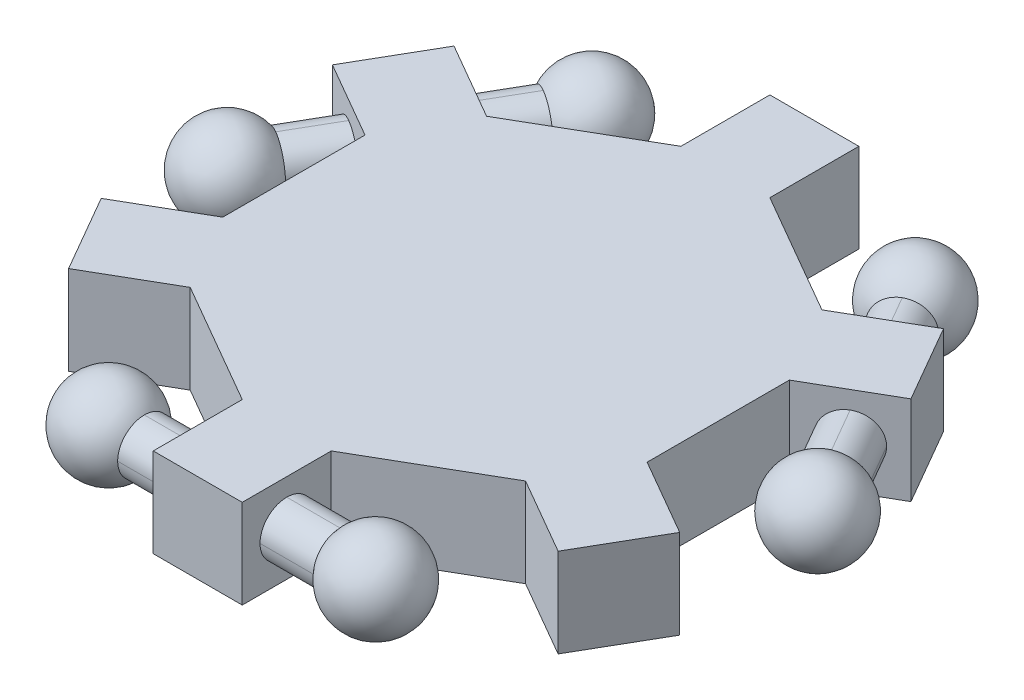
SolidWorks part; units mm, degrees
ref_plane "Front Plane" through (0, 0, 0) normal (0, 0, 1) x (1, 0, 0)
ref_plane "Top Plane" through (0, 0, 0) normal (0, 1, 0) x (1, 0, 0)
ref_plane "Right Plane" through (0, 0, 0) normal (1, 0, 0) x (0, 0, -1)
sketch "Sketch1" plane through (0, 0, 0) normal (0, 1, 0) x (1, 0, 0)
  line L0 (0, 210) -> (297, 0) construction
  line L1 (0, 0) -> (297, 0) construction
  line L2 (0, 0) -> (0, 210) construction
  line L3 (0, 210) -> (297, 210) construction
  line L4 (297, 0) -> (297, 210) construction
  line L5 (0, 0) -> (297, 210) construction
  dimension "D1" = 210
  dimension "D2" = 297
sketch "Sketch2" plane through (0, 0, 0) normal (0, 1, 0) x (1, 0, 0)
  line L0 (128.5, 139.641) -> (168.5, 139.641)
  line L1 (168.5, 139.641) -> (188.5, 105)
  line L2 (188.5, 105) -> (168.5, 70.359)
  line L3 (168.5, 70.359) -> (128.5, 70.359)
  line L4 (128.5, 70.359) -> (108.5, 105)
  line L5 (108.5, 105) -> (128.5, 139.641)
  line L6 (128.5, 139.641) -> (168.5, 70.359) construction
  line L7 (128.5, 70.359) -> (168.5, 139.641) construction
  line L8 (108.5, 105) -> (188.5, 105) construction
  line L9 (0, 0) -> (297, 0) construction
  line L10 (0, 210) -> (297, 0) construction
  line L11 (153.5, 139.641) -> (153.5, 129.641)
  line L12 (153.5, 129.641) -> (167.3397, 121.6506)
  line L13 (167.3397, 121.6506) -> (176, 126.6506)
  line L14 (143.5, 139.641) -> (143.5, 129.641)
  line L15 (143.5, 129.641) -> (129.6603, 121.6506)
  line L16 (129.6603, 121.6506) -> (121, 126.6506)
  line L17 (116, 117.9904) -> (128.9904, 110.4904)
  line L18 (128.9904, 110.4904) -> (124.6603, 97.0096)
  line L19 (124.6603, 97.0096) -> (116, 92.0096)
  line L20 (181, 117.9904) -> (172.3397, 112.9904)
  line L21 (172.3397, 112.9904) -> (172.3397, 97.0096)
  line L22 (172.3397, 97.0096) -> (181, 92.0096)
  line L23 (176, 83.3494) -> (167.3397, 88.3494)
  line L24 (167.3397, 88.3494) -> (153.5, 80.359)
  line L25 (153.5, 80.359) -> (153.5, 70.359)
  line L26 (121, 83.3494) -> (129.6603, 88.3494)
  line L27 (129.6603, 88.3494) -> (143.5, 80.359)
  line L28 (143.5, 80.359) -> (143.5, 70.359)
  point P2 (148.5, 105)
  point P11 (148.5, 105)
  dimension "D1" = 120
  dimension "D2" = 120
  dimension "D3" = 120
  dimension "D4" = 120
  dimension "D5" = 40
  dimension "D6" = 40
  dimension "D7" = 40
  dimension "D8" = 105
  dimension "D9" = 0
  dimension "D10" = 90
  dimension "D11" = 15
  dimension "D12" = 15
  dimension "D13" = 15
  dimension "D14" = 15
  dimension "D15" = 10
  dimension "D16" = 10
  dimension "D17" = 10
  dimension "D18" = 90
  dimension "D19" = 90
  dimension "D20" = 90
  dimension "D21" = 90
  dimension "D22" = 90
  dimension "D23" = 15
  dimension "D24" = 15
  dimension "D25" = 15
  dimension "D26" = 15
  dimension "D27" = 15
  dimension "D28" = 90
  dimension "D29" = 90
  dimension "D30" = 10
  dimension "D31" = 90
  dimension "D32" = 90
  dimension "D33" = 90
  dimension "D34" = 90
  dimension "D35" = 90
  dimension "D36" = 10
  dimension "D37" = 10
  dimension "D38" = 10
  dimension "D39" = 10
  dimension "D40" = 15
  dimension "D41" = 10
  dimension "D42" = 10
extrude "Boss-Extrude1" add sketch "Sketch2" along normal blind 10 contours L27 L28 L3 L25 L24 L23 L2 L22 L21 L20 L1 L13 L12 L11 L0 L14 L15 L16 L5 L17 L18 L19 L4 L26 region at (148.8166, 0, -104.9741)
sketch "Sketch3" plane through (153.5, 0, 0) normal (1, 0, 0) x (0, 0, -1)
  line L1 (0, 0) -> (210, 0) construction
  line L2 (80.359, 10) -> (80.359, 0) construction
  line L3 (72.359, 8) -> (78.359, 8)
  line L4 (72.359, 8) -> (72.359, 2)
  line L5 (72.359, 2) -> (78.359, 2)
  line L6 (78.359, 8) -> (78.359, 2)
  line L7 (72.359, 8) -> (78.359, 2) construction
  line L8 (78.359, 8) -> (72.359, 2) construction
  dimension "D1" = 6
  dimension "D2" = 6
  dimension "D3" = 2
  dimension "D4" = 2
extrude "Boss-Extrude2" add sketch "Sketch3" along normal blind 10
fillet "Fillet1" radius 3 4 edges at (158.5, 8, -72.359) (158.5, 2, -72.359) (158.5, 2, -78.359) (158.5, 8, -78.359)
sketch "Sketch4" plane through (163.5, 0, 0) normal (1, 0, 0) x (0, 0, -1)
  line L0 (70.359, 5) -> (80.359, 5)
  line L1 (72.359, 8) -> (78.359, 2) construction
  arc A0 (80.359, 5) -> (70.359, 5) centre (75.359, 5) ccw
  point P4 (0, 0)
  point P7 (75.359, 5)
  dimension "D2" = 0
  dimension "D1" = 0
revolve "Revolve1" add sketch "Sketch4" angle 360 about L0 region at (163.5, 6.2732, -75.359)
ref_plane "Plane1" through (148.5, 0, 0) normal (-1, 0, 0) x (0, 0, 1)
ref_plane "Plane2" through (-8.3413, 0, -14.4476) normal (0.5, 0, 0.866) x (0.866, 0, -0.5)
mirror "Mirror1" about plane through (148.5, 0, 0) normal (-1, 0, 0) of bodies 108 104
mirror "Mirror2" about plane through (-8.3413, 0, -14.4476) normal (0.5, 0, 0.866) of bodies 105
mirror "Mirror3" about plane through (148.5, 0, 0) normal (-1, 0, 0) of bodies 106
